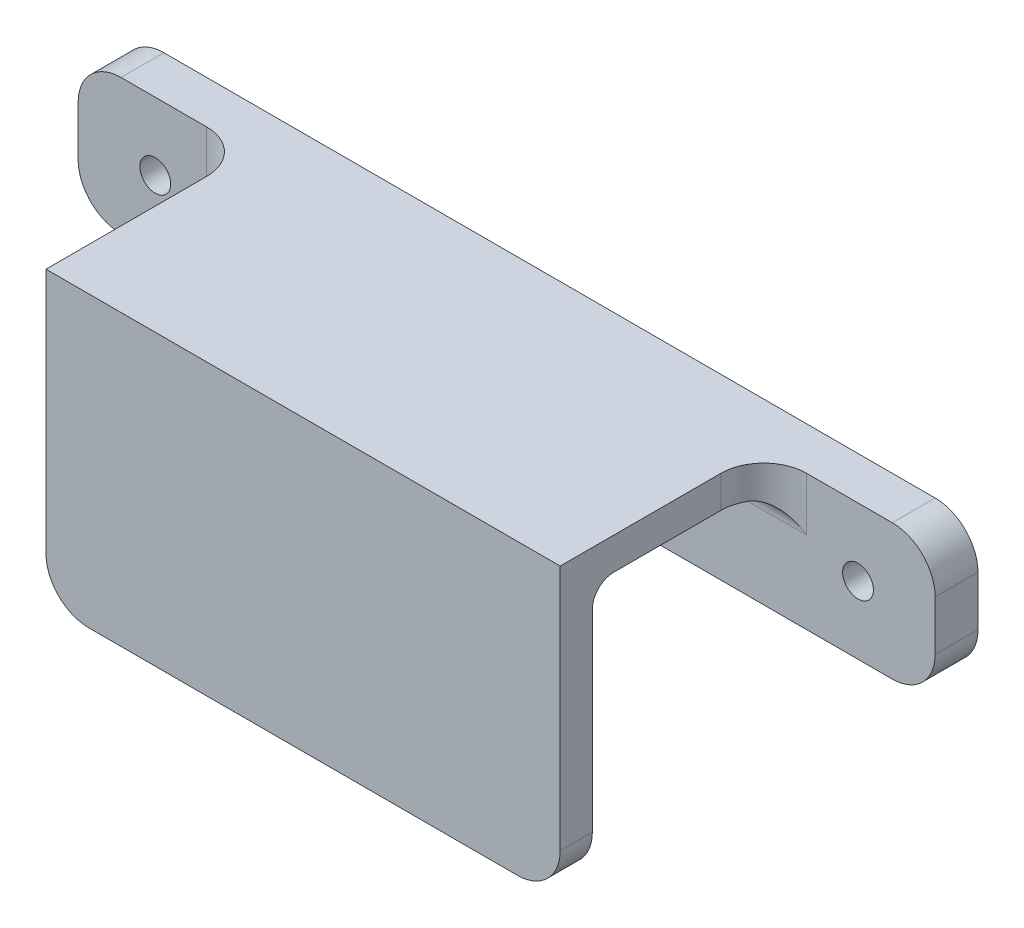
SolidWorks part; units mm, degrees
ref_plane "Front Plane" through (0, 0, 0) normal (0, 0, 1) x (1, 0, 0)
ref_plane "Top Plane" through (0, 0, 0) normal (0, 1, 0) x (1, 0, 0)
ref_plane "Right Plane" through (0, 0, 0) normal (1, 0, 0) x (0, 0, -1)
sketch "Sketch1" plane through (0, 0, 0) normal (0, 0, 1) x (1, 0, 0)
  line L1 (-63.5, -10.033) -> (63.5, -10.033)
  line L2 (-63.5, -10.033) -> (-63.5, 10.033)
  line L3 (-63.5, 10.033) -> (63.5, 10.033)
  line L4 (63.5, -10.033) -> (63.5, 10.033)
  line L5 (-63.5, -10.033) -> (63.5, 10.033) construction
  line L6 (-63.5, 10.033) -> (63.5, -10.033) construction
  point P0 (0, 0)
  dimension "D1" = 20.066
  dimension "D2" = 127
extrude "Boss-Extrude1" add sketch "Sketch1" along normal blind 6.35
sketch "Sketch2" plane through (0, 0, 6.35) normal (0, 0, 1) x (1, 0, 0)
  line L0 (63.5, 10.033) -> (-63.5, 10.033) construction
  line L1 (-38.1, 10.033) -> (38.1, 10.033)
  line L2 (-38.1, 10.033) -> (-38.1, 5.2705)
  line L3 (-38.1, 5.2705) -> (38.1, 5.2705)
  line L4 (38.1, 10.033) -> (38.1, 5.2705)
  dimension "D1" = 38.1
  dimension "D2" = 38.1
  dimension "D3" = 4.7625
extrude "Boss-Extrude2" add sketch "Sketch2" along normal blind 25.4
sketch "Sketch4" plane through (0, 0, 31.75) normal (0, 0, 1) x (1, 0, 0)
  line L1 (-38.1, 10.033) -> (38.1, 10.033)
  line L2 (-38.1, 10.033) -> (-38.1, -32.8295)
  line L3 (-38.1, -32.8295) -> (38.1, -32.8295)
  line L4 (38.1, 10.033) -> (38.1, -32.8295)
  line L5 (-38.1, 5.2705) -> (38.1, 5.2705) construction
  dimension "D1" = 38.1
extrude "Boss-Extrude3" add sketch "Sketch4" along normal blind 4.7625
sketch "Sketch6" plane through (0, 0, 0) normal (0, 0, -1) x (-1, 0, 0)
  line L0 (-63.5, 0) -> (63.5, 0) construction
  line L1 (-63.5, -10.033) -> (-63.5, 10.033) construction
  line L2 (63.5, 10.033) -> (63.5, -10.033) construction
  circle A0 centre (-52.07, 0) radius 2.286
  circle A1 centre (52.07, 0) radius 2.286
  dimension "D1" = 4.572
  dimension "D2" = 11.43
  dimension "D3" = 11.43
extrude "Cut-Extrude1" cut sketch "Sketch6" against normal through all
fillet "Fillet1" radius 6.35 4 edges at (-63.5, 10.033, 3.175) (-63.5, -10.033, 3.175) (63.5, -10.033, 3.175) (63.5, 10.033, 3.175)
fillet "Fillet5" radius 6.35 2 edges at (-38.1, -32.8295, 34.1313) (38.1, -32.8295, 34.1313)
fillet "Fillet6" radius 3.175 2 edges at (0, 5.2705, 6.35) (0, 5.2705, 31.75)
fillet "Fillet7" radius 6.35 2 edges at (-38.1, 6.0643, 6.35) (38.1, 6.0642, 6.35)
